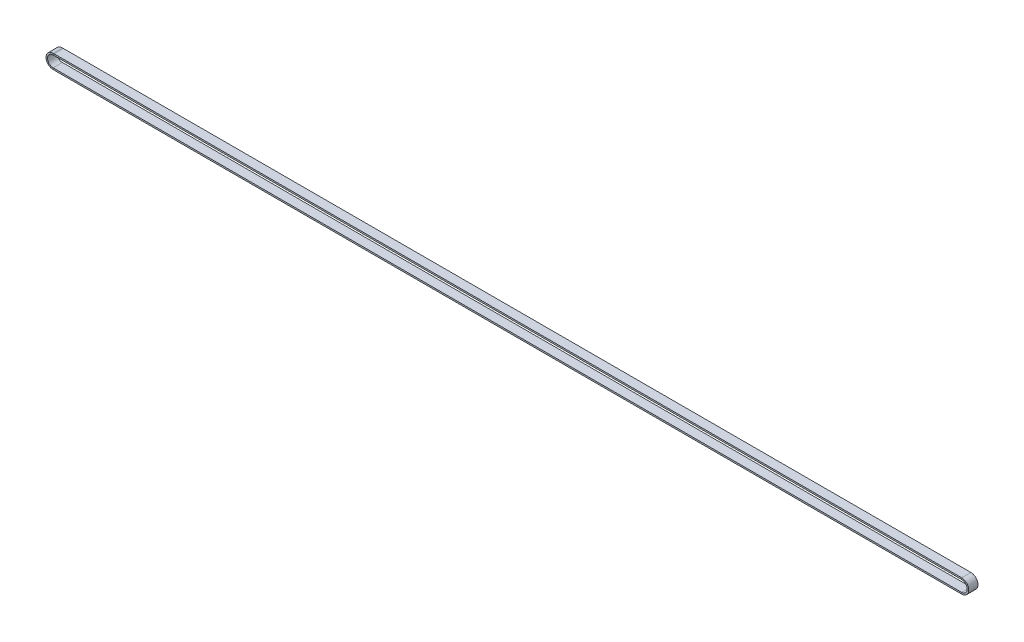
SolidWorks part; units mm, degrees
ref_plane "Front Plane" through (0, 0, 0) normal (0, 0, 1) x (1, 0, 0)
ref_plane "Top Plane" through (0, 0, 0) normal (0, 1, 0) x (1, 0, 0)
ref_plane "Right Plane" through (0, 0, 0) normal (1, 0, 0) x (0, 0, -1)
sketch "Sketch2" plane through (0, 0, -48.4834) normal (0, 0, 1) x (1, 0, 0)
  line L0 (0, 0) -> (1, 0) construction
  line L1 (0, 0) -> (0, 1) construction
  line L2 (-1, -56.8446) -> (883.5206, -56.8446)
  line L3 (883.5206, -70.6446) -> (-1, -70.6446)
  arc A0 (-1, -70.6446) -> (-1, -56.8446) centre (-1, -63.7446) cw
  arc A1 (883.5206, -56.8446) -> (883.5206, -70.6446) centre (883.5206, -63.7446) cw
sketch "Sketch3" plane through (0, 0, 0) normal (1, 0, 0) x (0, 0, -1)
  line L1 (48.4834, -58.3446) -> (39.4834, -58.3446)
  line L2 (48.4834, -58.3446) -> (48.4834, -56.8446)
  line L3 (48.4834, -56.8446) -> (39.4834, -56.8446)
  line L4 (39.4834, -58.3446) -> (39.4834, -56.8446)
  dimension "D1" = 9
  dimension "D2" = 1.5
sweep "Sweep1" add profiles "Sketch3" path "Sketch2"
